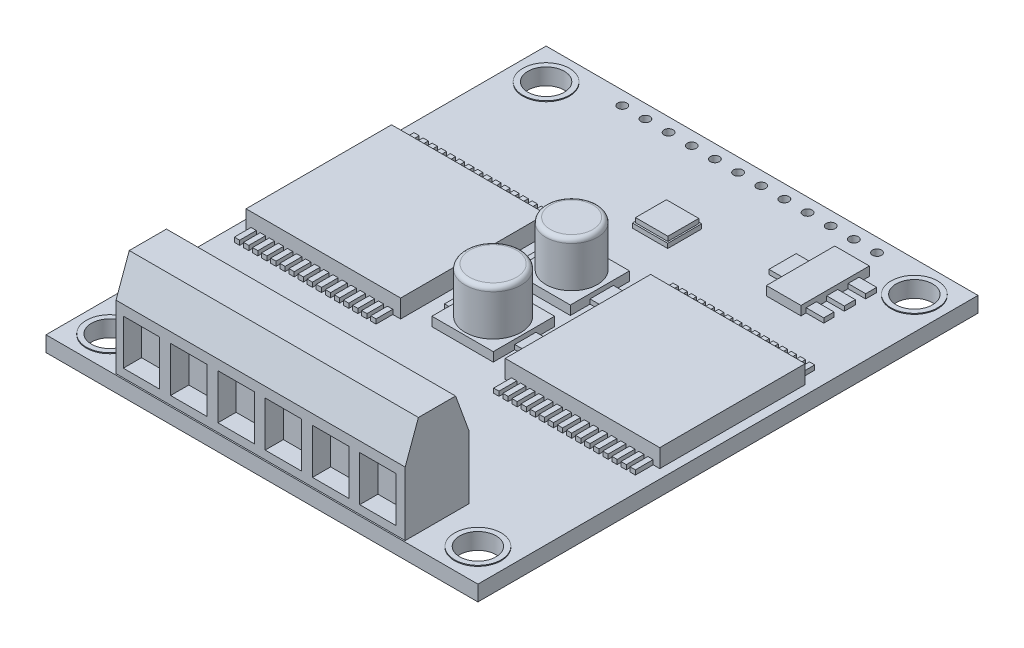
SolidWorks part; units mm, degrees
ref_plane "Plano frontal" through (0, 0, 0) normal (0, 0, 1) x (1, 0, 0)
ref_plane "Plano superior" through (0, 0, 0) normal (0, 1, 0) x (1, 0, 0)
ref_plane "Plano direito" through (0, 0, 0) normal (1, 0, 0) x (0, 0, -1)
sketch "Esboço1" plane through (0, 0, 0) normal (0, 1, 0) x (1, 0, 0)
  line L1 (0, 0) -> (47.5, 0)
  line L2 (0, 0) -> (0, 55)
  line L3 (0, 55) -> (47.5, 55)
  line L4 (47.5, 0) -> (47.5, 55)
  dimension "D1" = 47.5
  dimension "D2" = 55
extrude "Ressalto-extrusão1" add sketch "Esboço1" along normal blind 1.7
sketch "Esboço2" plane through (0, 1.7, 0) normal (0, 1, 0) x (1, 0, 0)
  line L0 (23.75, 55) -> (23.75, 0) construction
  line L1 (47.5, 55) -> (0, 55) construction
  line L2 (0, 55) -> (0, 0) construction
  line L3 (0, 0) -> (47.5, 0) construction
  line L4 (0, 27.5) -> (47.5, 27.5) construction
  line L5 (47.5, 0) -> (47.5, 55) construction
  circle A0 centre (3.5, 51.5) radius 2
  circle A1 centre (44, 51.5) radius 2
  circle A2 centre (3.5, 3.5) radius 2
  circle A3 centre (44, 3.5) radius 2
  circle A4 centre (12.5, 4.25) radius 1.25
  circle A5 centre (17, 4.25) radius 1.25
  circle A6 centre (21.5, 4.25) radius 1.25
  circle A7 centre (26, 4.25) radius 1.25
  circle A8 centre (30.5, 4.25) radius 1.25
  circle A9 centre (35, 4.25) radius 1.25
  circle A10 centre (9.862, 53.5151) radius 0.5
  circle A11 centre (12.4091, 53.5151) radius 0.5
  circle A12 centre (14.9562, 53.5151) radius 0.5
  circle A13 centre (17.5033, 53.5151) radius 0.5
  circle A14 centre (20.0504, 53.5151) radius 0.5
  circle A15 centre (22.5975, 53.5151) radius 0.5
  circle A16 centre (25.1445, 53.5151) radius 0.5
  circle A17 centre (27.6916, 53.5151) radius 0.5
  circle A18 centre (30.2387, 53.5151) radius 0.5
  circle A19 centre (32.7858, 53.5151) radius 0.5
  circle A20 centre (35.3329, 53.5151) radius 0.5
  circle A21 centre (37.88, 53.5151) radius 0.5
  dimension "D1" = 4
  dimension "D2" = 3.5
  dimension "D3" = 3.5
  dimension "D4" = 2.5
  dimension "D5" = 4.25
  dimension "D6" = 12.5
  dimension "D8" = 12
  dimension "D9" = 9.62
  dimension "D10" = 9.862
  dimension "D7" = 6
extrude "Corte-extrusão1" cut sketch "Esboço2" against normal through all
sketch "Esboço3" plane through (0, 1.7, 0) normal (0, 1, 0) x (1, 0, 0)
  line L0 (0, 0) -> (47.5, 0) construction
  line L1 (1, 21) -> (18, 21)
  line L2 (1, 21) -> (1, 37)
  line L3 (1, 37) -> (18, 37)
  line L4 (18, 21) -> (18, 37)
  line L5 (0, 55) -> (0, 0) construction
  line L6 (23.75, 55) -> (23.75, 0) construction
  line L7 (47.5, 55) -> (0, 55) construction
  line L8 (29.5, 21) -> (29.5, 37)
  line L9 (46.5, 37) -> (29.5, 37)
  line L10 (46.5, 21) -> (46.5, 37)
  line L11 (46.5, 21) -> (29.5, 21)
  line L12 (24.1185, 12.484) -> (18.9057, 12.484)
  line L13 (31.7432, 12.4451) -> (26.5304, 12.4451)
  line L14 (31.7432, 12.4451) -> (31.7432, 7.5435)
  line L15 (31.7432, 7.5435) -> (26.5304, 7.5435)
  line L16 (26.5304, 12.4451) -> (26.5304, 7.5435)
  line L17 (24.1185, 12.484) -> (24.1185, 7.5824)
  line L18 (24.1185, 7.5824) -> (18.9057, 7.5824)
  line L19 (18.9057, 12.484) -> (18.9057, 7.5824)
  dimension "D1" = 16
  dimension "D2" = 17
  dimension "D3" = 21
  dimension "D4" = 1
extrude "Ressalto-extrusão2" add sketch "Esboço3" along normal blind 2
sketch "Esboço4" plane through (0, 1.7, 0) normal (0, 1, 0) x (1, 0, 0)
  line L0 (23.75, 55) -> (23.75, 0) construction
  line L1 (47.5, 55) -> (0, 55) construction
  line L2 (0, 0) -> (47.5, 0) construction
  line L3 (20.4546, 28.7336) -> (27.201, 28.7336)
  line L4 (20.5, 37.1687) -> (27, 37.1687)
  line L5 (20.5, 37.1687) -> (20.5, 30.6687)
  line L6 (20.5, 30.6687) -> (27, 30.6687)
  line L7 (27, 37.1687) -> (27, 30.6687)
  line L8 (20.5, 37.1687) -> (27, 30.6687) construction
  line L9 (20.5, 30.6687) -> (27, 37.1687) construction
  line L10 (20.4546, 28.7336) -> (20.4546, 21.9872)
  line L11 (20.4546, 21.9872) -> (27.201, 21.9872)
  line L12 (27.201, 28.7336) -> (27.201, 21.9872)
  line L13 (20.4546, 28.7336) -> (27.201, 21.9872) construction
  line L14 (20.4546, 21.9872) -> (27.201, 28.7336) construction
  line L16 (22.254, 45.9774) -> (25.812, 45.9774)
  line L17 (22.254, 45.9774) -> (22.254, 42.5811)
  line L18 (22.254, 42.5811) -> (25.812, 42.5811)
  line L19 (25.812, 45.9774) -> (25.812, 42.5811)
  line L20 (35.92, 50.8293) -> (39.7206, 50.8293)
  line L21 (35.92, 50.8293) -> (35.92, 43.3089)
  line L22 (35.92, 43.3089) -> (39.7206, 43.3089)
  line L23 (39.7206, 50.8293) -> (39.7206, 43.3089)
  point P6 (23.75, 33.9187)
  point P11 (23.8278, 25.3604)
  dimension "D1" = 6.5
  dimension "D2" = 6.5
extrude "Ressalto-extrusão3" add sketch "Esboço4" along normal blind 1
sketch "Esboço5" plane through (0, 2.7, 0) normal (0, 1, 0) x (1, 0, 0)
  circle A0 centre (23.7095, 34.1008) radius 2.8359
  circle A1 centre (23.8232, 25.3492) radius 3.0751
extrude "Ressalto-extrusão4" add sketch "Esboço5" along normal blind 5
sketch "Esboço6" plane through (0, 1.7, 0) normal (0, 1, 0) x (1, 0, 0)
  line L1 (30.9079, 11.8227) -> (34.02, 11.8227)
  line L2 (30.9079, 11.8227) -> (30.9079, 10.8891)
  line L3 (30.9079, 10.8891) -> (34.02, 10.8891)
  line L4 (34.02, 11.8227) -> (34.02, 10.8891)
  line L5 (30.9079, 9.333) -> (34.02, 9.333)
  line L6 (30.9079, 9.333) -> (30.9079, 8.3994)
  line L7 (30.9079, 8.3994) -> (34.02, 8.3994)
  line L8 (34.02, 9.333) -> (34.02, 8.3994)
  line L9 (27.0955, 11.8227) -> (25.6951, 11.8227)
  line L10 (27.0955, 11.8227) -> (27.0955, 8.3994)
  line L11 (27.0955, 8.3994) -> (25.6951, 8.3994)
  line L12 (25.6951, 11.8227) -> (25.6951, 8.3994)
  line L13 (23.2054, 11.8227) -> (24.8392, 11.8227)
  line L14 (23.2054, 11.8227) -> (23.2054, 8.3994)
  line L15 (23.2054, 8.3994) -> (24.8392, 8.3994)
  line L16 (24.8392, 11.8227) -> (24.8392, 8.3994)
  line L17 (19.4708, 11.8227) -> (16.6699, 11.8227)
  line L18 (19.4708, 11.8227) -> (19.4708, 10.8891)
  line L19 (19.4708, 10.8891) -> (16.6699, 10.8891)
  line L20 (16.6699, 11.8227) -> (16.6699, 10.8891)
  line L21 (19.4708, 9.333) -> (16.6699, 9.333)
  line L22 (19.4708, 9.333) -> (19.4708, 8.3994)
  line L23 (19.4708, 8.3994) -> (16.6699, 8.3994)
  line L24 (16.6699, 9.333) -> (16.6699, 8.3994)
  line L25 (25.6951, 26.6831) -> (28.0292, 26.6831)
  line L26 (25.6951, 26.6831) -> (25.6951, 24.349)
  line L27 (25.6951, 24.349) -> (28.0292, 24.349)
  line L28 (28.0292, 26.6831) -> (28.0292, 24.349)
  line L29 (21.4937, 26.6831) -> (19.4708, 26.6831)
  line L30 (21.4937, 26.6831) -> (21.4937, 24.349)
  line L31 (21.4937, 24.349) -> (19.4708, 24.349)
  line L32 (19.4708, 26.6831) -> (19.4708, 24.349)
  line L33 (25.6951, 35.397) -> (28.0292, 35.397)
  line L34 (25.6951, 35.397) -> (25.6951, 32.8295)
  line L35 (25.6951, 32.8295) -> (28.0292, 32.8295)
  line L36 (28.0292, 35.397) -> (28.0292, 32.8295)
  line L37 (21.4937, 35.397) -> (19.4708, 35.397)
  line L38 (21.4937, 35.397) -> (21.4937, 32.8295)
  line L39 (21.4937, 32.8295) -> (19.4708, 32.8295)
  line L40 (19.4708, 35.397) -> (19.4708, 32.8295)
  line L41 (38.8311, 49.6972) -> (41.6614, 49.6972)
  line L42 (38.8311, 49.6972) -> (38.8311, 48.4842)
  line L43 (38.8311, 48.4842) -> (41.6614, 48.4842)
  line L44 (41.6614, 49.6972) -> (41.6614, 48.4842)
  line L45 (38.8311, 47.3521) -> (41.6614, 47.3521)
  line L46 (38.8311, 47.3521) -> (38.8311, 46.1391)
  line L47 (38.8311, 46.1391) -> (41.6614, 46.1391)
  line L48 (41.6614, 47.3521) -> (41.6614, 46.1391)
  line L49 (38.8311, 45.0071) -> (41.6614, 45.0071)
  line L50 (38.8311, 45.0071) -> (38.8311, 43.875)
  line L51 (38.8311, 43.875) -> (41.6614, 43.875)
  line L52 (41.6614, 45.0071) -> (41.6614, 43.875)
  line L53 (36.6478, 48.4842) -> (34.02, 48.4842)
  line L54 (36.6478, 48.4842) -> (36.6478, 45.4922)
  line L55 (36.6478, 45.4922) -> (34.02, 45.4922)
  line L56 (34.02, 48.4842) -> (34.02, 45.4922)
  line L57 (22.1003, 46.1391) -> (25.9772, 46.1391)
  line L58 (22.1003, 46.1391) -> (22.1003, 42.3999)
  line L59 (22.1003, 42.3999) -> (25.9772, 42.3999)
  line L60 (25.9772, 46.1391) -> (25.9772, 42.3999)
  line B0 (2.5528, 19.1607) -> (3.1376, 19.1607)
  line B1 (1.5528, 19.1607) -> (2.1376, 19.1607)
  line B2 (1.5528, 19.1607) -> (1.5528, 21.5534)
  line B3 (1.5528, 21.5534) -> (2.1376, 21.5534)
  line B4 (2.1376, 19.1607) -> (2.1376, 21.5534)
  line B5 (2.5528, 19.1607) -> (2.5528, 21.5534)
  line B6 (2.5528, 21.5534) -> (3.1376, 21.5534)
  line B7 (3.1376, 19.1607) -> (3.1376, 21.5534)
  line B8 (3.5528, 19.1607) -> (4.1376, 19.1607)
  line B9 (3.5528, 19.1607) -> (3.5528, 21.5534)
  line B10 (3.5528, 21.5534) -> (4.1376, 21.5534)
  line B11 (4.1376, 19.1607) -> (4.1376, 21.5534)
  line B12 (4.5528, 19.1607) -> (5.1376, 19.1607)
  line B13 (4.5528, 19.1607) -> (4.5528, 21.5534)
  line B14 (4.5528, 21.5534) -> (5.1376, 21.5534)
  line B15 (5.1376, 19.1607) -> (5.1376, 21.5534)
  line B16 (5.5528, 19.1607) -> (6.1376, 19.1607)
  line B17 (5.5528, 19.1607) -> (5.5528, 21.5534)
  line B18 (5.5528, 21.5534) -> (6.1376, 21.5534)
  line B19 (6.1376, 19.1607) -> (6.1376, 21.5534)
  line B20 (6.5528, 19.1607) -> (7.1376, 19.1607)
  line B21 (6.5528, 19.1607) -> (6.5528, 21.5534)
  line B22 (6.5528, 21.5534) -> (7.1376, 21.5534)
  line B23 (7.1376, 19.1607) -> (7.1376, 21.5534)
  line B24 (7.5528, 19.1607) -> (8.1376, 19.1607)
  line B25 (7.5528, 19.1607) -> (7.5528, 21.5534)
  line B26 (7.5528, 21.5534) -> (8.1376, 21.5534)
  line B27 (8.1376, 19.1607) -> (8.1376, 21.5534)
  line B28 (8.5528, 19.1607) -> (9.1376, 19.1607)
  line B29 (8.5528, 19.1607) -> (8.5528, 21.5534)
  line B30 (8.5528, 21.5534) -> (9.1376, 21.5534)
  line B31 (9.1376, 19.1607) -> (9.1376, 21.5534)
  line B32 (9.5528, 19.1607) -> (10.1376, 19.1607)
  line B33 (9.5528, 19.1607) -> (9.5528, 21.5534)
  line B34 (9.5528, 21.5534) -> (10.1376, 21.5534)
  line B35 (10.1376, 19.1607) -> (10.1376, 21.5534)
  line B36 (10.5528, 19.1607) -> (11.1376, 19.1607)
  line B37 (10.5528, 19.1607) -> (10.5528, 21.5534)
  line B38 (10.5528, 21.5534) -> (11.1376, 21.5534)
  line B39 (11.1376, 19.1607) -> (11.1376, 21.5534)
  line B40 (11.5528, 19.1607) -> (12.1376, 19.1607)
  line B41 (11.5528, 19.1607) -> (11.5528, 21.5534)
  line B42 (11.5528, 21.5534) -> (12.1376, 21.5534)
  line B43 (12.1376, 19.1607) -> (12.1376, 21.5534)
  line B44 (12.5528, 19.1607) -> (13.1376, 19.1607)
  line B45 (12.5528, 19.1607) -> (12.5528, 21.5534)
  line B46 (12.5528, 21.5534) -> (13.1376, 21.5534)
  line B47 (13.1376, 19.1607) -> (13.1376, 21.5534)
  line B48 (13.5528, 19.1607) -> (14.1376, 19.1607)
  line B49 (13.5528, 19.1607) -> (13.5528, 21.5534)
  line B50 (13.5528, 21.5534) -> (14.1376, 21.5534)
  line B51 (14.1376, 19.1607) -> (14.1376, 21.5534)
  line B52 (14.5528, 19.1607) -> (15.1376, 19.1607)
  line B53 (14.5528, 19.1607) -> (14.5528, 21.5534)
  line B54 (14.5528, 21.5534) -> (15.1376, 21.5534)
  line B55 (15.1376, 19.1607) -> (15.1376, 21.5534)
  line B56 (15.5528, 19.1607) -> (16.1376, 19.1607)
  line B57 (15.5528, 19.1607) -> (15.5528, 21.5534)
  line B58 (15.5528, 21.5534) -> (16.1376, 21.5534)
  line B59 (16.1376, 19.1607) -> (16.1376, 21.5534)
  line B60 (16.5528, 19.1607) -> (17.1376, 19.1607)
  line B61 (16.5528, 19.1607) -> (16.5528, 21.5534)
  line B62 (16.5528, 21.5534) -> (17.1376, 21.5534)
  line B63 (17.1376, 19.1607) -> (17.1376, 21.5534)
  line B64 (2.4754, 36.593) -> (3.0603, 36.593)
  line B65 (1.4754, 36.593) -> (2.0603, 36.593)
  line B66 (1.4754, 36.593) -> (1.4754, 38.9857)
  line B67 (1.4754, 38.9857) -> (2.0603, 38.9857)
  line B68 (2.0603, 36.593) -> (2.0603, 38.9857)
  line B69 (2.4754, 36.593) -> (2.4754, 38.9857)
  line B70 (2.4754, 38.9857) -> (3.0603, 38.9857)
  line B71 (3.0603, 36.593) -> (3.0603, 38.9857)
  line B72 (3.4754, 36.593) -> (4.0603, 36.593)
  line B73 (3.4754, 36.593) -> (3.4754, 38.9857)
  line B74 (3.4754, 38.9857) -> (4.0603, 38.9857)
  line B75 (4.0603, 36.593) -> (4.0603, 38.9857)
  line B76 (4.4754, 36.593) -> (5.0603, 36.593)
  line B77 (4.4754, 36.593) -> (4.4754, 38.9857)
  line B78 (4.4754, 38.9857) -> (5.0603, 38.9857)
  line B79 (5.0603, 36.593) -> (5.0603, 38.9857)
  line B80 (5.4754, 36.593) -> (6.0603, 36.593)
  line B81 (5.4754, 36.593) -> (5.4754, 38.9857)
  line B82 (5.4754, 38.9857) -> (6.0603, 38.9857)
  line B83 (6.0603, 36.593) -> (6.0603, 38.9857)
  line B84 (6.4754, 36.593) -> (7.0603, 36.593)
  line B85 (6.4754, 36.593) -> (6.4754, 38.9857)
  line B86 (6.4754, 38.9857) -> (7.0603, 38.9857)
  line B87 (7.0603, 36.593) -> (7.0603, 38.9857)
  line B88 (7.4754, 36.593) -> (8.0603, 36.593)
  line B89 (7.4754, 36.593) -> (7.4754, 38.9857)
  line B90 (7.4754, 38.9857) -> (8.0603, 38.9857)
  line B91 (8.0603, 36.593) -> (8.0603, 38.9857)
  line B92 (8.4754, 36.593) -> (9.0603, 36.593)
  line B93 (8.4754, 36.593) -> (8.4754, 38.9857)
  line B94 (8.4754, 38.9857) -> (9.0603, 38.9857)
  line B95 (9.0603, 36.593) -> (9.0603, 38.9857)
  line B96 (9.4754, 36.593) -> (10.0603, 36.593)
  line B97 (9.4754, 36.593) -> (9.4754, 38.9857)
  line B98 (9.4754, 38.9857) -> (10.0603, 38.9857)
  line B99 (10.0603, 36.593) -> (10.0603, 38.9857)
  line B100 (10.4754, 36.593) -> (11.0603, 36.593)
  line B101 (10.4754, 36.593) -> (10.4754, 38.9857)
  line B102 (10.4754, 38.9857) -> (11.0603, 38.9857)
  line B103 (11.0603, 36.593) -> (11.0603, 38.9857)
  line B104 (11.4754, 36.593) -> (12.0603, 36.593)
  line B105 (11.4754, 36.593) -> (11.4754, 38.9857)
  line B106 (11.4754, 38.9857) -> (12.0603, 38.9857)
  line B107 (12.0603, 36.593) -> (12.0603, 38.9857)
  line B108 (12.4754, 36.593) -> (13.0603, 36.593)
  line B109 (12.4754, 36.593) -> (12.4754, 38.9857)
  line B110 (12.4754, 38.9857) -> (13.0603, 38.9857)
  line B111 (13.0603, 36.593) -> (13.0603, 38.9857)
  line B112 (13.4754, 36.593) -> (14.0603, 36.593)
  line B113 (13.4754, 36.593) -> (13.4754, 38.9857)
  line B114 (13.4754, 38.9857) -> (14.0603, 38.9857)
  line B115 (14.0603, 36.593) -> (14.0603, 38.9857)
  line B116 (14.4754, 36.593) -> (15.0603, 36.593)
  line B117 (14.4754, 36.593) -> (14.4754, 38.9857)
  line B118 (14.4754, 38.9857) -> (15.0603, 38.9857)
  line B119 (15.0603, 36.593) -> (15.0603, 38.9857)
  line B120 (15.4754, 36.593) -> (16.0603, 36.593)
  line B121 (15.4754, 36.593) -> (15.4754, 38.9857)
  line B122 (15.4754, 38.9857) -> (16.0603, 38.9857)
  line B123 (16.0603, 36.593) -> (16.0603, 38.9857)
  line B124 (16.4754, 36.593) -> (17.0603, 36.593)
  line B125 (16.4754, 36.593) -> (16.4754, 38.9857)
  line B126 (16.4754, 38.9857) -> (17.0603, 38.9857)
  line B127 (17.0603, 36.593) -> (17.0603, 38.9857)
  line B128 (31.1926, 19.0407) -> (31.7775, 19.0407)
  line B129 (30.1926, 19.0407) -> (30.7775, 19.0407)
  line B130 (30.1926, 19.0407) -> (30.1926, 21.4333)
  line B131 (30.1926, 21.4333) -> (30.7775, 21.4333)
  line B132 (30.7775, 19.0407) -> (30.7775, 21.4333)
  line B133 (31.1926, 19.0407) -> (31.1926, 21.4333)
  line B134 (31.1926, 21.4333) -> (31.7775, 21.4333)
  line B135 (31.7775, 19.0407) -> (31.7775, 21.4333)
  line B136 (32.1926, 19.0407) -> (32.7775, 19.0407)
  line B137 (32.1926, 19.0407) -> (32.1926, 21.4333)
  line B138 (32.1926, 21.4333) -> (32.7775, 21.4333)
  line B139 (32.7775, 19.0407) -> (32.7775, 21.4333)
  line B140 (33.1926, 19.0407) -> (33.7775, 19.0407)
  line B141 (33.1926, 19.0407) -> (33.1926, 21.4333)
  line B142 (33.1926, 21.4333) -> (33.7775, 21.4333)
  line B143 (33.7775, 19.0407) -> (33.7775, 21.4333)
  line B144 (34.1926, 19.0407) -> (34.7775, 19.0407)
  line B145 (34.1926, 19.0407) -> (34.1926, 21.4333)
  line B146 (34.1926, 21.4333) -> (34.7775, 21.4333)
  line B147 (34.7775, 19.0407) -> (34.7775, 21.4333)
  line B148 (35.1926, 19.0407) -> (35.7775, 19.0407)
  line B149 (35.1926, 19.0407) -> (35.1926, 21.4333)
  line B150 (35.1926, 21.4333) -> (35.7775, 21.4333)
  line B151 (35.7775, 19.0407) -> (35.7775, 21.4333)
  line B152 (36.1926, 19.0407) -> (36.7775, 19.0407)
  line B153 (36.1926, 19.0407) -> (36.1926, 21.4333)
  line B154 (36.1926, 21.4333) -> (36.7775, 21.4333)
  line B155 (36.7775, 19.0407) -> (36.7775, 21.4333)
  line B156 (37.1926, 19.0407) -> (37.7775, 19.0407)
  line B157 (37.1926, 19.0407) -> (37.1926, 21.4333)
  line B158 (37.1926, 21.4333) -> (37.7775, 21.4333)
  line B159 (37.7775, 19.0407) -> (37.7775, 21.4333)
  line B160 (38.1926, 19.0407) -> (38.7775, 19.0407)
  line B161 (38.1926, 19.0407) -> (38.1926, 21.4333)
  line B162 (38.1926, 21.4333) -> (38.7775, 21.4333)
  line B163 (38.7775, 19.0407) -> (38.7775, 21.4333)
  line B164 (39.1926, 19.0407) -> (39.7775, 19.0407)
  line B165 (39.1926, 19.0407) -> (39.1926, 21.4333)
  line B166 (39.1926, 21.4333) -> (39.7775, 21.4333)
  line B167 (39.7775, 19.0407) -> (39.7775, 21.4333)
  line B168 (40.1926, 19.0407) -> (40.7775, 19.0407)
  line B169 (40.1926, 19.0407) -> (40.1926, 21.4333)
  line B170 (40.1926, 21.4333) -> (40.7775, 21.4333)
  line B171 (40.7775, 19.0407) -> (40.7775, 21.4333)
  line B172 (41.1926, 19.0407) -> (41.7775, 19.0407)
  line B173 (41.1926, 19.0407) -> (41.1926, 21.4333)
  line B174 (41.1926, 21.4333) -> (41.7775, 21.4333)
  line B175 (41.7775, 19.0407) -> (41.7775, 21.4333)
  line B176 (42.1926, 19.0407) -> (42.7775, 19.0407)
  line B177 (42.1926, 19.0407) -> (42.1926, 21.4333)
  line B178 (42.1926, 21.4333) -> (42.7775, 21.4333)
  line B179 (42.7775, 19.0407) -> (42.7775, 21.4333)
  line B180 (43.1926, 19.0407) -> (43.7775, 19.0407)
  line B181 (43.1926, 19.0407) -> (43.1926, 21.4333)
  line B182 (43.1926, 21.4333) -> (43.7775, 21.4333)
  line B183 (43.7775, 19.0407) -> (43.7775, 21.4333)
  line B184 (44.1926, 19.0407) -> (44.7775, 19.0407)
  line B185 (44.1926, 19.0407) -> (44.1926, 21.4333)
  line B186 (44.1926, 21.4333) -> (44.7775, 21.4333)
  line B187 (44.7775, 19.0407) -> (44.7775, 21.4333)
  line B188 (45.1926, 19.0407) -> (45.7775, 19.0407)
  line B189 (45.1926, 19.0407) -> (45.1926, 21.4333)
  line B190 (45.1926, 21.4333) -> (45.7775, 21.4333)
  line B191 (45.7775, 19.0407) -> (45.7775, 21.4333)
  line B192 (31.057, 36.5113) -> (31.6418, 36.5113)
  line B193 (30.057, 36.5113) -> (30.6418, 36.5113)
  line B194 (30.057, 36.5113) -> (30.057, 38.904)
  line B195 (30.057, 38.904) -> (30.6418, 38.904)
  line B196 (30.6418, 36.5113) -> (30.6418, 38.904)
  line B197 (31.057, 36.5113) -> (31.057, 38.904)
  line B198 (31.057, 38.904) -> (31.6418, 38.904)
  line B199 (31.6418, 36.5113) -> (31.6418, 38.904)
  line B200 (32.057, 36.5113) -> (32.6418, 36.5113)
  line B201 (32.057, 36.5113) -> (32.057, 38.904)
  line B202 (32.057, 38.904) -> (32.6418, 38.904)
  line B203 (32.6418, 36.5113) -> (32.6418, 38.904)
  line B204 (33.057, 36.5113) -> (33.6418, 36.5113)
  line B205 (33.057, 36.5113) -> (33.057, 38.904)
  line B206 (33.057, 38.904) -> (33.6418, 38.904)
  line B207 (33.6418, 36.5113) -> (33.6418, 38.904)
  line B208 (34.057, 36.5113) -> (34.6418, 36.5113)
  line B209 (34.057, 36.5113) -> (34.057, 38.904)
  line B210 (34.057, 38.904) -> (34.6418, 38.904)
  line B211 (34.6418, 36.5113) -> (34.6418, 38.904)
  line B212 (35.057, 36.5113) -> (35.6418, 36.5113)
  line B213 (35.057, 36.5113) -> (35.057, 38.904)
  line B214 (35.057, 38.904) -> (35.6418, 38.904)
  line B215 (35.6418, 36.5113) -> (35.6418, 38.904)
  line B216 (36.057, 36.5113) -> (36.6418, 36.5113)
  line B217 (36.057, 36.5113) -> (36.057, 38.904)
  line B218 (36.057, 38.904) -> (36.6418, 38.904)
  line B219 (36.6418, 36.5113) -> (36.6418, 38.904)
  line B220 (37.057, 36.5113) -> (37.6418, 36.5113)
  line B221 (37.057, 36.5113) -> (37.057, 38.904)
  line B222 (37.057, 38.904) -> (37.6418, 38.904)
  line B223 (37.6418, 36.5113) -> (37.6418, 38.904)
  line B224 (38.057, 36.5113) -> (38.6418, 36.5113)
  line B225 (38.057, 36.5113) -> (38.057, 38.904)
  line B226 (38.057, 38.904) -> (38.6418, 38.904)
  line B227 (38.6418, 36.5113) -> (38.6418, 38.904)
  line B228 (39.057, 36.5113) -> (39.6418, 36.5113)
  line B229 (39.057, 36.5113) -> (39.057, 38.904)
  line B230 (39.057, 38.904) -> (39.6418, 38.904)
  line B231 (39.6418, 36.5113) -> (39.6418, 38.904)
  line B232 (40.057, 36.5113) -> (40.6418, 36.5113)
  line B233 (40.057, 36.5113) -> (40.057, 38.904)
  line B234 (40.057, 38.904) -> (40.6418, 38.904)
  line B235 (40.6418, 36.5113) -> (40.6418, 38.904)
  line B236 (41.057, 36.5113) -> (41.6418, 36.5113)
  line B237 (41.057, 36.5113) -> (41.057, 38.904)
  line B238 (41.057, 38.904) -> (41.6418, 38.904)
  line B239 (41.6418, 36.5113) -> (41.6418, 38.904)
  line B240 (42.057, 36.5113) -> (42.6418, 36.5113)
  line B241 (42.057, 36.5113) -> (42.057, 38.904)
  line B242 (42.057, 38.904) -> (42.6418, 38.904)
  line B243 (42.6418, 36.5113) -> (42.6418, 38.904)
  line B244 (43.057, 36.5113) -> (43.6418, 36.5113)
  line B245 (43.057, 36.5113) -> (43.057, 38.904)
  line B246 (43.057, 38.904) -> (43.6418, 38.904)
  line B247 (43.6418, 36.5113) -> (43.6418, 38.904)
  line B248 (44.057, 36.5113) -> (44.6418, 36.5113)
  line B249 (44.057, 36.5113) -> (44.057, 38.904)
  line B250 (44.057, 38.904) -> (44.6418, 38.904)
  line B251 (44.6418, 36.5113) -> (44.6418, 38.904)
  line B252 (45.057, 36.5113) -> (45.6418, 36.5113)
  line B253 (45.057, 36.5113) -> (45.057, 38.904)
  line B254 (45.057, 38.904) -> (45.6418, 38.904)
  line B255 (45.6418, 36.5113) -> (45.6418, 38.904)
sketch_block_instance "Bloco1-1"
sketch_block "Bloco1"
sketch_block_instance "Bloco1-2"
sketch_block_instance "Bloco1-3"
sketch_block_instance "Bloco1-4"
extrude "Ressalto-extrusão5" add sketch "Esboço6" along normal blind 0.5
fillet "Filete1" radius 0.5 2 edges at (23.7095, 7.7, -31.2649) (23.8232, 7.7, -22.2741)
sketch "Esboço7" plane through (0, 1.7, 0) normal (0, 1, 0) x (1, 0, 0)
  circle A0 centre (3.5, 3.5) radius 2.562
  circle A1 centre (12.5, 4.25) radius 1.4927
  circle A2 centre (44, 3.5) radius 2.562
  circle A3 centre (3.5, 51.5) radius 2.562
  circle A4 centre (44, 51.5) radius 2.562
  circle A5 centre (17, 4.25) radius 1.4927
  circle A6 centre (21.5, 4.25) radius 1.4927
  circle A7 centre (26, 4.25) radius 1.4927
  circle A8 centre (30.5, 4.25) radius 1.4927
  circle A9 centre (35, 4.25) radius 1.4927
  circle A10 centre (3.5, 3.5) radius 2
  circle A11 centre (44, 3.5) radius 2
  circle A12 centre (3.5, 51.5) radius 2
  circle A13 centre (44, 51.5) radius 2
  circle A14 centre (12.5, 4.25) radius 1.25
  circle A15 centre (17, 4.25) radius 1.25
  circle A16 centre (21.5, 4.25) radius 1.25
  circle A17 centre (26, 4.25) radius 1.25
  circle A18 centre (30.5, 4.25) radius 1.25
  circle A19 centre (35, 4.25) radius 1.25
extrude "Ressalto-extrusão6" add sketch "Esboço7" along normal blind 0.1
sketch "Esboço8" plane through (0, 1.7, 0) normal (0, 1, 0) x (1, 0, 0)
  line L1 (7.5546, 0.1471) -> (39.3546, 0.1471)
  line L2 (7.5546, 0.1471) -> (7.5546, 7.1471)
  line L3 (7.5546, 7.1471) -> (39.3546, 7.1471)
  line L4 (39.3546, 0.1471) -> (39.3546, 7.1471)
  dimension "D1" = 7
  dimension "D2" = 31.8
extrude "Ressalto-extrusão7" add sketch "Esboço8" along normal blind 11
chamfer "Chanfro1" distance 4 angle 20 2 edges at (23.4546, 12.7, -7.1471) (23.4546, 12.7, -0.1471) first distance on face at (23.4546, 7.2, -7.1471) first distance on face at (23.4546, 7.2, -0.1471)
sketch "Esboço10" plane through (0, 0, -0.1471) normal (0, 0, 1) x (1, 0, 0)
  line L0 (13.558, 7.5855) -> (17.558, 7.5855)
  line L1 (8.358, 7.5855) -> (12.358, 7.5855)
  line L2 (8.358, 7.5855) -> (8.358, 2.6205)
  line L3 (8.358, 2.6205) -> (12.358, 2.6205)
  line L4 (12.358, 7.5855) -> (12.358, 2.6205)
  line L5 (13.558, 7.5855) -> (13.558, 2.6205)
  line L6 (13.558, 2.6205) -> (17.558, 2.6205)
  line L7 (17.558, 7.5855) -> (17.558, 2.6205)
  line L8 (18.758, 7.5855) -> (22.758, 7.5855)
  line L9 (18.758, 7.5855) -> (18.758, 2.6205)
  line L10 (18.758, 2.6205) -> (22.758, 2.6205)
  line L11 (22.758, 7.5855) -> (22.758, 2.6205)
  line L12 (23.958, 7.5855) -> (27.958, 7.5855)
  line L13 (23.958, 7.5855) -> (23.958, 2.6205)
  line L14 (23.958, 2.6205) -> (27.958, 2.6205)
  line L15 (27.958, 7.5855) -> (27.958, 2.6205)
  line L16 (29.158, 7.5855) -> (33.158, 7.5855)
  line L17 (29.158, 7.5855) -> (29.158, 2.6205)
  line L18 (29.158, 2.6205) -> (33.158, 2.6205)
  line L19 (33.158, 7.5855) -> (33.158, 2.6205)
  line L20 (34.358, 7.5855) -> (38.358, 7.5855)
  line L21 (34.358, 7.5855) -> (34.358, 2.6205)
  line L22 (34.358, 2.6205) -> (38.358, 2.6205)
  line L23 (38.358, 7.5855) -> (38.358, 2.6205)
  dimension "D1" = 4
  dimension "D3" = 1.2
  dimension "D2" = 6
extrude "Corte-extrusão2" cut sketch "Esboço10" against normal blind 2
